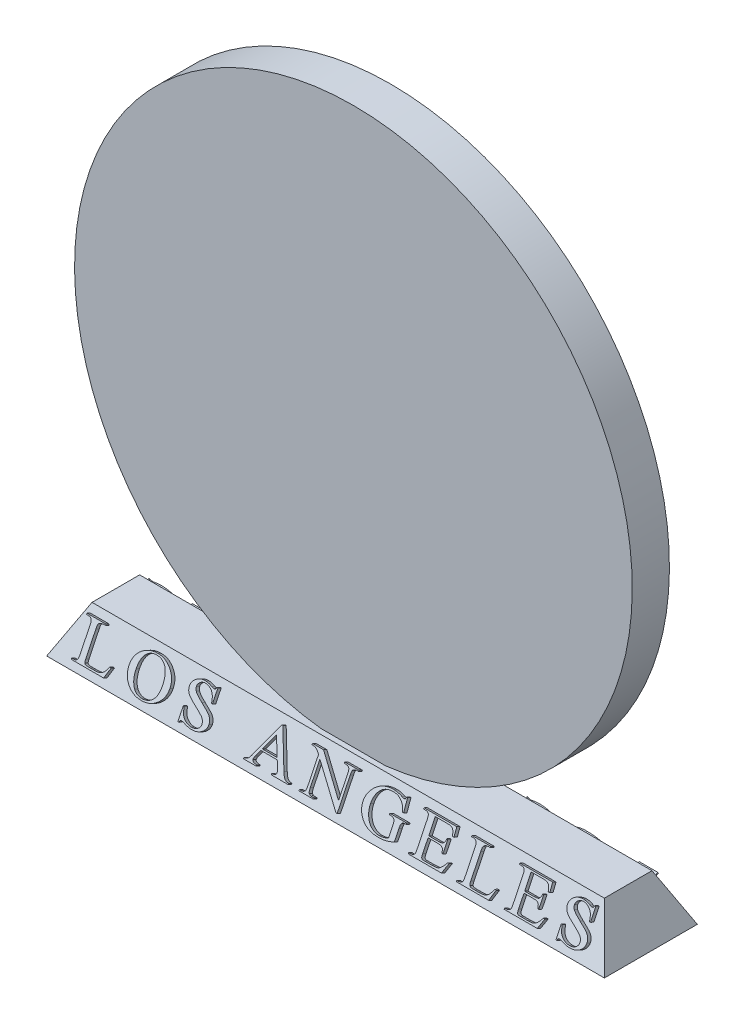
SolidWorks part; units mm, degrees
ref_plane "Front Plane" through (0, 0, 0) normal (0, 0, 1) x (1, 0, 0)
ref_plane "Top Plane" through (0, 0, 0) normal (0, 1, 0) x (1, 0, 0)
ref_plane "Right Plane" through (0, 0, 0) normal (1, 0, 0) x (0, 0, -1)
sketch "Sketch1" plane through (0, 0, 0) normal (0, 1, 0) x (1, 0, 0)
  line L1 (38.1, -6.35) -> (-38.1, -6.35)
  line L2 (38.1, -6.35) -> (38.1, 6.35)
  line L3 (38.1, 6.35) -> (-38.1, 6.35)
  line L4 (-38.1, -6.35) -> (-38.1, 6.35)
  line L5 (38.1, -6.35) -> (-38.1, 6.35) construction
  line L6 (38.1, 6.35) -> (-38.1, -6.35) construction
  point P0 (0, 0)
extrude "Boss-Extrude1" add sketch "Sketch1" along normal blind 6.35 draft 26
sketch "Sketch2" plane through (0, 0, 0) normal (0, 0, 1) x (1, 0, 0)
  circle A0 centre (0, 44.196) radius 38.1
extrude "Boss-Extrude2" add sketch "Sketch2" along normal blind 2.54 and the other way blind 2.54
sketch "Sketch5" plane through (0, 2.5019, 5.1297) normal (0, 0.4384, 0.8988) x (1, 0, 0)
  text T0 "LOS ANGELES" font "Times New Roman" height in points 20
sketch "Sketch6" plane through (0, 2.5019, -5.1297) normal (0, 0.4384, -0.8988) x (-1, 0, 0)
  text T0 "LOS ANGELES" font "Times New Roman" height in points 20
extrude "Boss-Extrude3" add sketch "Sketch5" along normal blind 0.508
extrude "Boss-Extrude4" add sketch "Sketch6" along normal blind 0.508
